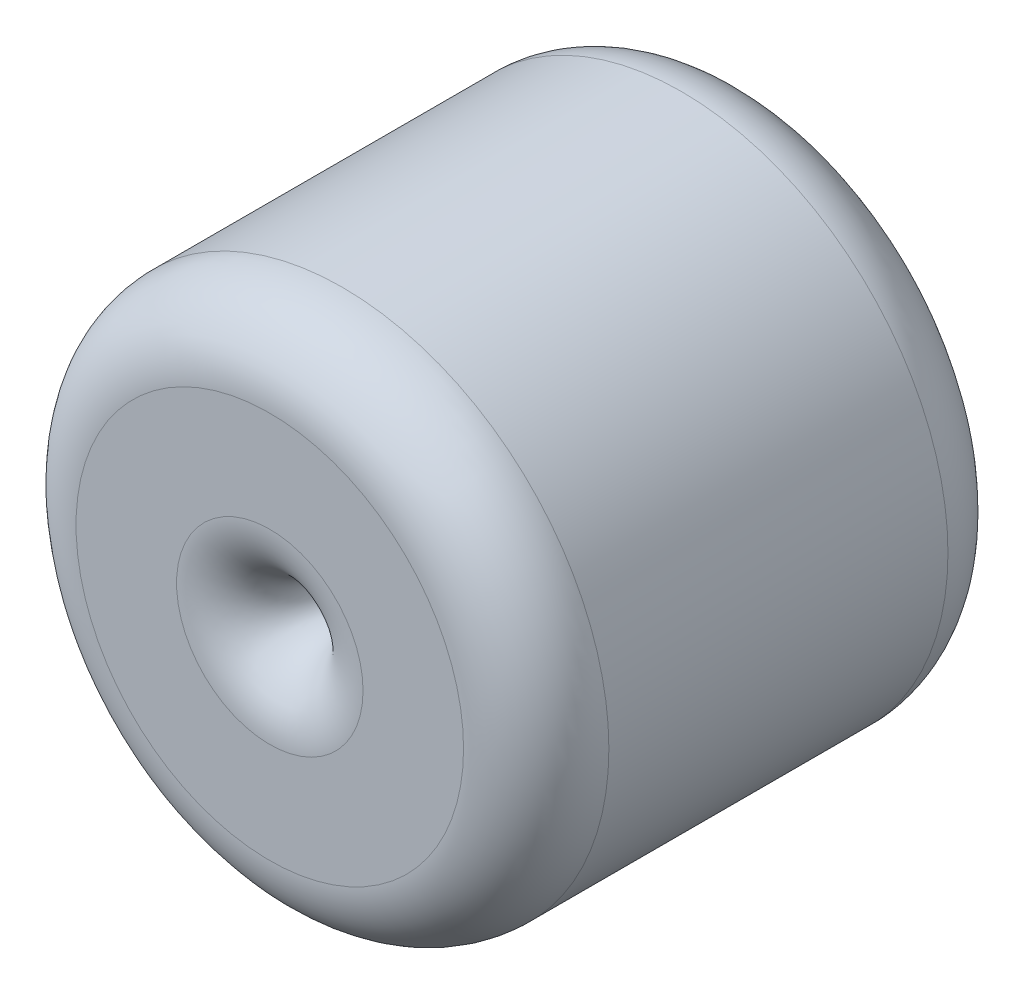
SolidWorks part; units mm, degrees
ref_plane "前视基准面" through (0, 0, 0) normal (0, 0, 1) x (1, 0, 0)
ref_plane "上视基准面" through (0, 0, 0) normal (0, 1, 0) x (1, 0, 0)
ref_plane "右视基准面" through (0, 0, 0) normal (1, 0, 0) x (0, 0, -1)
other "Configuration Table"
sketch "草图1" plane through (0, 0, 0) normal (0, 0, 1) x (1, 0, 0)
  circle A0 centre (0, 0) radius 22
  circle A1 centre (0, 0) radius 1.7
extrude "凸台-拉伸1" add sketch "草图1" along normal mid plane 40
fillet "圆角1" radius 6 4 edges at (1.7, 0, -20) (1.7, 0, 20) (22, 0, -20) (22, 0, 20) tangent propagation no
